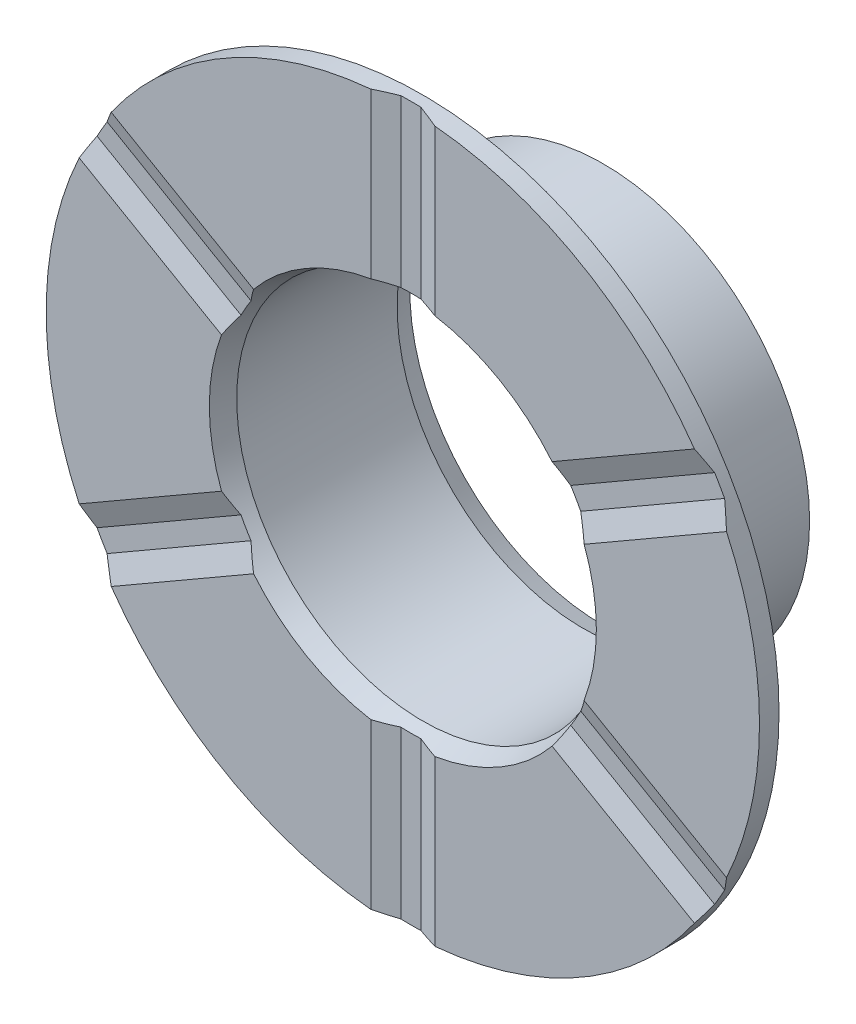
SolidWorks part; units mm, degrees
ref_plane "Front" through (0, 0, 0) normal (0, 0, 1) x (1, 0, 0)
ref_plane "Top" through (0, 0, 0) normal (0, 1, 0) x (1, 0, 0)
ref_plane "Right" through (0, 0, 0) normal (1, 0, 0) x (0, 0, -1)
sketch "Sketch1" plane through (0, 0, 0) normal (0, 0, 1) x (1, 0, 0)
  circle A0 centre (0, 0) radius 18.575
  circle A1 centre (0, 0) radius 20.575
  dimension "D1" = 37.15
  dimension "D2" = 2
extrude "Boss-Extrude1" add sketch "Sketch1" along normal blind 20
sketch "Sketch2" plane through (0, 0, 20) normal (0, 0, 1) x (1, 0, 0)
  circle A0 centre (0, 0) radius 35.575
  circle A1 centre (0, 0) radius 20.575
  circle A2 centre (0, 0) radius 20.575
  dimension "D1" = 0
  dimension "D2" = 15
extrude "Boss-Extrude2" add sketch "Sketch2" against normal blind 1.95
chamfer "Chamfer2" distance 2 angle 20 2 edges at (18.575, 0, 20) (18.575, 0, 0) first distance on face at (18.575, 0, 20)
sketch "Sketch3" plane through (0, 0, 20) normal (0, 0, 1) x (1, 0, 0)
  line L0 (0, 0) -> (0, 35.575) construction
  line L2 (-1, 36.575) -> (1, 36.575)
  line L3 (-1, 36.575) -> (-1, 18.575)
  line L4 (-1, 18.575) -> (1, 18.575)
  line L5 (1, 36.575) -> (1, 18.575)
  line L6 (-1, 36.575) -> (1, 18.575) construction
  line L7 (-1, 18.575) -> (1, 36.575) construction
  circle A0 centre (0, 0) radius 35.575 construction
  circle A3 centre (0, 0) radius 18.575 construction
  point P6 (0, 27.575)
  dimension "D1" = 18
  dimension "D2" = 2
extrude "Cut-Extrude1" cut sketch "Sketch3" against normal blind 0.8
chamfer "Chamfer3" distance 0.8 angle 70 2 edges at (1, 27.419, 20) (-1, 27.419, 20) first distance on face at (1, 27.3096, 19.5) first distance on face at (-1, 27.3825, 19.7)
pattern_circular "CirPattern2" count 6 over 360 about axis through (0, 0, 20) along (0, 0, -1) of "Chamfer3", "Cut-Extrude1" reverse direction yes
